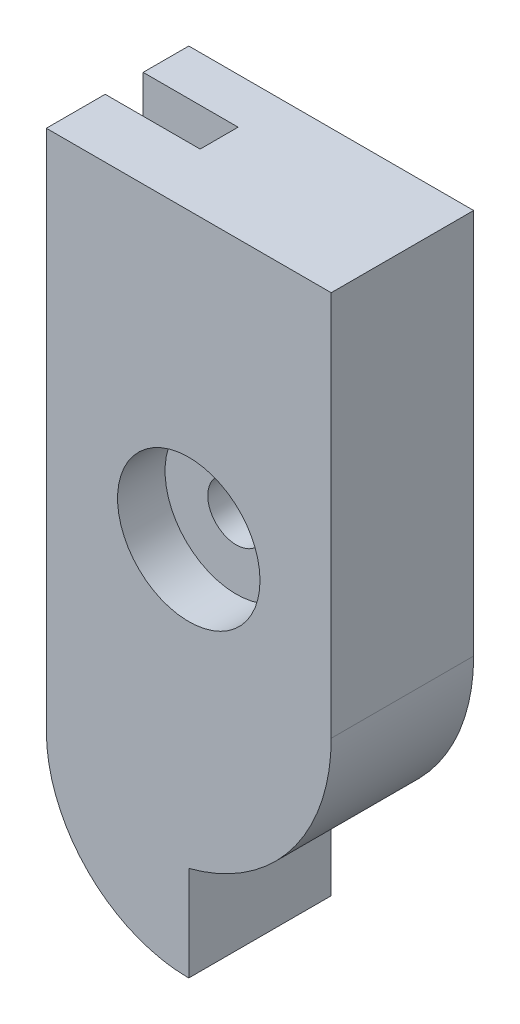
SolidWorks part; units mm, degrees
ref_plane "Ebene vorne" through (0, 0, 0) normal (0, 0, 1) x (1, 0, 0)
ref_plane "Ebene oben" through (0, 0, 0) normal (0, 1, 0) x (1, 0, 0)
ref_plane "Ebene rechts" through (0, 0, 0) normal (1, 0, 0) x (0, 0, -1)
sketch "Sketch1" plane through (0, 0, 0) normal (0, 0, 1) x (1, 0, 0)
  line L0 (-15, 0) -> (15, 0) construction
  line L1 (-15, 30) -> (15, 30)
  line L2 (-15, 30) -> (-15, -30)
  line L3 (-15, -30) -> (15, -30)
  line L4 (15, 30) -> (15, -30)
  line L5 (0, -30) -> (0, 30) construction
  point P9 (0, 0)
  dimension "D1" = 30
  dimension "D2" = 60
extrude "Boss-Extrude1" add sketch "Sketch1" along normal mid plane 15 contours L1 L4 L3 L2
sketch "Sketch3" plane through (0, 0, 0) normal (1, 0, 0) x (0, 0, -1)
  line L0 (-7.5, -7.5) -> (-2.5, -7.5)
  line L1 (-2.5, -7.5) -> (-2.5, -3)
  line L2 (-2.5, -3) -> (2.5, -3)
  line L3 (2.5, -3) -> (2.5, -7.5)
  line L4 (2.5, -7.5) -> (7.5, -7.5)
  line L5 (-7.5, 30) -> (-7.5, -30) construction
  line L6 (-19.1694, 0) -> (24.4545, 0) construction
  line L7 (-7.5, -7.5) -> (-7.5, 0)
  line L8 (7.5, -7.5) -> (7.5, 0)
  line L9 (-7.5, 0) -> (7.5, 0)
  dimension "D1" = 5
  dimension "D2" = 5
  dimension "D3" = 15
  dimension "D4" = 7.5
  dimension "D5" = 3
revolve "Cut-Revolve1" cut sketch "Sketch3" angle 360 about L6
sketch "Sketch4" plane through (-15, 0, 0) normal (-1, 0, 0) x (0, 0, 1)
  line L0 (7.5, 30) -> (-7.5, 30) construction
  line L1 (-2.6959, 30) -> (1.3041, 30)
  line L2 (-2.6959, 30) -> (-2.6959, -30)
  line L3 (-2.6959, -30) -> (1.3041, -30)
  line L4 (1.3041, 30) -> (1.3041, -30)
  line L5 (7.5, -30) -> (-7.5, -30) construction
  line L6 (-0.6959, 30) -> (-0.6959, -30) construction
  dimension "D1" = 4
extrude "Cut-Extrude1" cut sketch "Sketch4" against normal blind 10
sketch "Sketch5" plane through (0, 0, -7.5) normal (0, 0, 1) x (1, 0, 0)
  line L0 (0, -5.5) -> (-15, -0.0404)
  line L2 (-15, 30) -> (-15, -30) construction
  line L3 (0, -4.0953) -> (-15, 1.3643)
  line L5 (0, -5.5) -> (-15, -5.5) construction
  line L6 (0, -55) -> (0, 55) construction
  line L7 (-15, 1.3643) -> (-15, -0.0404)
  line L8 (0, -4.0953) -> (0, -5.5)
  circle A0 centre (0, 0) radius 5.5 construction
  point P12 (-7.5, -2.7702)
  dimension "D1" = 11
  dimension "D2" = 1.32
  dimension "D3" = 20
extrude "Cut-Extrude2" cut sketch "Sketch5" along normal blind 3
sketch "Sketch7" plane through (0, -30, 0) normal (0, -1, 0) x (1, 0, 0)
  line L0 (-15, -7.5) -> (15, -7.5) construction
  line L1 (0, -7.5) -> (-15, -7.5)
  line L2 (0, -7.5) -> (0, 7.5)
  line L3 (0, 7.5) -> (-15, 7.5)
  line L4 (-15, -7.5) -> (-15, 7.5)
extrude "Boss-Extrude4" add sketch "Sketch7" along normal blind 10
fillet "Fillet3" radius 15 1 edges at (-15, -40, 0) first distance on face at (-15, -1.446, -2.232)
fillet "Fillet4" radius 20 1 edges at (15, -30, 0)
